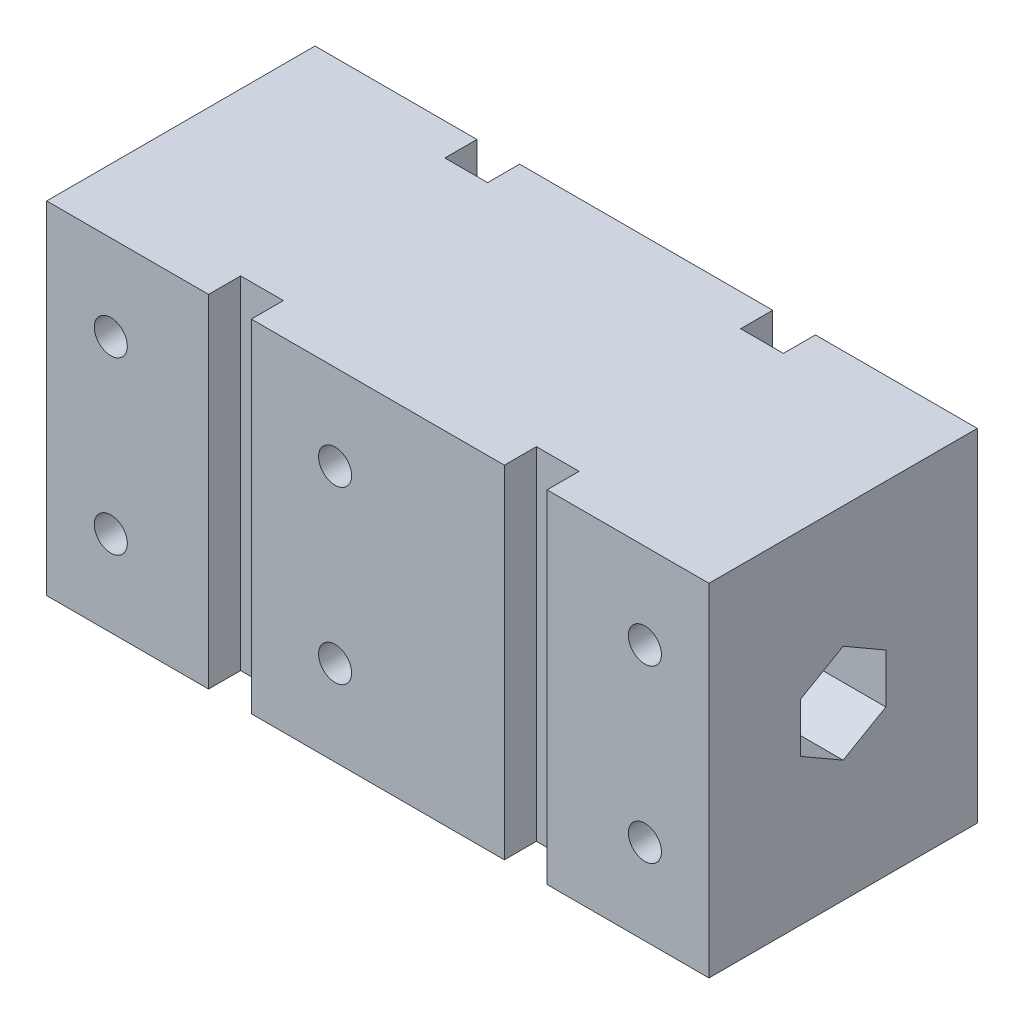
SolidWorks part; units mm, degrees
material "PET"
ref_plane "Front" through (0, 0, 0) normal (0, 0, 1) x (1, 0, 0)
ref_plane "Top" through (0, 0, 0) normal (0, 1, 0) x (1, 0, 0)
ref_plane "Right" through (0, 0, 0) normal (1, 0, 0) x (0, 0, -1)
sketch "Sketch1" plane through (0, 0, 0) normal (1, 0, 0) x (0, 0, -1)
  line L1 (19.939, -25.4) -> (-19.939, -25.4)
  line L2 (19.939, -25.4) -> (19.939, 25.4)
  line L3 (19.939, 25.4) -> (-19.939, 25.4)
  line L4 (-19.939, -25.4) -> (-19.939, 25.4)
  line L5 (19.939, -25.4) -> (-19.939, 25.4) construction
  line L6 (19.939, 25.4) -> (-19.939, -25.4) construction
  point P0 (0, 0)
  dimension "D1" = 50.8
  dimension "D2" = 39.878
extrude "Boss-Extrude1" add sketch "Sketch1" along normal blind 98.425
sketch "Sketch3" plane through (98.425, 0, 0) normal (1, 0, 0) x (0, 0, -1)
  line L1 (6.35, 3.6662) -> (0, 7.3323)
  line L2 (0, 7.3323) -> (-6.35, 3.6662)
  line L3 (-6.35, 3.6662) -> (-6.35, -3.6662)
  line L4 (-6.35, -3.6662) -> (0, -7.3323)
  line L5 (0, -7.3323) -> (6.35, -3.6662)
  line L6 (6.35, -3.6662) -> (6.35, 3.6662)
  circle A0 centre (0, 0) radius 6.35 construction
  dimension "D1" = 12.7
extrude "Cut-Extrude2" cut sketch "Sketch3" against normal through all
ref_axis "Axis1" through (-80.9, 0, 0) along (1, 0, 0)
sketch "Sketch4" plane through (0, 25.4, 0) normal (0, 1, 0) x (1, 0, 0)
  line L0 (98.425, 19.939) -> (0, 19.939) construction
  line L1 (24.0589, -19.939) -> (30.4089, -19.939)
  line L2 (24.0589, -19.939) -> (24.0589, -15.1765)
  line L3 (24.0589, -15.1765) -> (30.4089, -15.1765)
  line L4 (30.4089, -19.939) -> (30.4089, -15.1765)
  line L5 (24.0589, -19.939) -> (30.4089, -15.1765) construction
  line L6 (24.0589, -15.1765) -> (30.4089, -19.939) construction
  line L7 (68.0161, -15.1765) -> (74.3661, -15.1765)
  line L8 (68.0161, -15.1765) -> (68.0161, -19.939)
  line L9 (68.0161, -19.939) -> (74.3661, -19.939)
  line L10 (74.3661, -15.1765) -> (74.3661, -19.939)
  line L11 (68.0161, -15.1765) -> (74.3661, -19.939) construction
  line L12 (68.0161, -19.939) -> (74.3661, -15.1765) construction
  line L13 (68.0161, 19.939) -> (74.3661, 19.939)
  line L14 (68.0161, 19.939) -> (68.0161, 15.1765)
  line L15 (68.0161, 15.1765) -> (74.3661, 15.1765)
  line L16 (74.3661, 19.939) -> (74.3661, 15.1765)
  line L17 (68.0161, 19.939) -> (74.3661, 15.1765) construction
  line L18 (68.0161, 15.1765) -> (74.3661, 19.939) construction
  line L19 (24.0589, 19.939) -> (30.4089, 19.939)
  line L20 (24.0589, 19.939) -> (24.0589, 15.1765)
  line L21 (24.0589, 15.1765) -> (30.4089, 15.1765)
  line L22 (30.4089, 19.939) -> (30.4089, 15.1765)
  line L23 (24.0589, 19.939) -> (30.4089, 15.1765) construction
  line L24 (24.0589, 15.1765) -> (30.4089, 19.939) construction
  line L25 (98.425, 19.939) -> (98.425, -19.939) construction
  line L26 (0, 19.939) -> (0, -19.939) construction
  line L29 (98.425, -19.939) -> (0, -19.939) construction
  point P0 (27.2339, -17.5578)
  point P5 (71.1911, -17.5578)
  point P10 (71.1911, 17.5577)
  point P15 (27.2339, 17.5577)
  dimension "D1" = 24.0589
  dimension "D2" = 6.35
  dimension "D3" = 4.7625
  dimension "D4" = 24.0589
extrude "Cut-Extrude3" cut sketch "Sketch4" against normal through all
sketch "Sketch7" plane through (0, 0, 19.939) normal (0, 0, 1) x (1, 0, 0)
  line L0 (98.425, 25.4) -> (74.3661, 25.4) construction
  line L1 (0, 25.4) -> (0, -25.4) construction
  line L2 (98.425, 25.4) -> (98.425, -25.4) construction
  point P0 (9.525, 12.7)
  point P2 (42.861, 12.7)
  point P4 (88.9, 12.7)
  point P6 (88.9, -12.7)
  point P8 (42.861, -12.7)
  point P10 (9.525, -12.7)
  dimension "D1" = 25.4
  dimension "D2" = 12.7
  dimension "D3" = 9.525
  dimension "D4" = 9.525
hole_wizard "#10 (0.1935) Diameter Hole1" positions "Sketch7" profile "Sketch6" hole size "#10" standard "ANSI Inch" end condition up to next
sketch "Sketch6" plane through (9.525, 12.7, 19.939) normal (1, 0, 0) x (0, -1, 0)
  line L0 (0, 0) -> (0, 39.878)
  line L1 (0, 39.878) -> (2.4574, 39.878)
  line L2 (2.4574, 39.878) -> (2.4574, 0)
  line L5 (2.4574, 0) -> (0, 0)
  line L11 (0, -6.35) -> (0, 107.95) construction
  dimension "Thru Hole Dia." = 4.9149
  dimension "Thru Hole Depth" = 39.878
